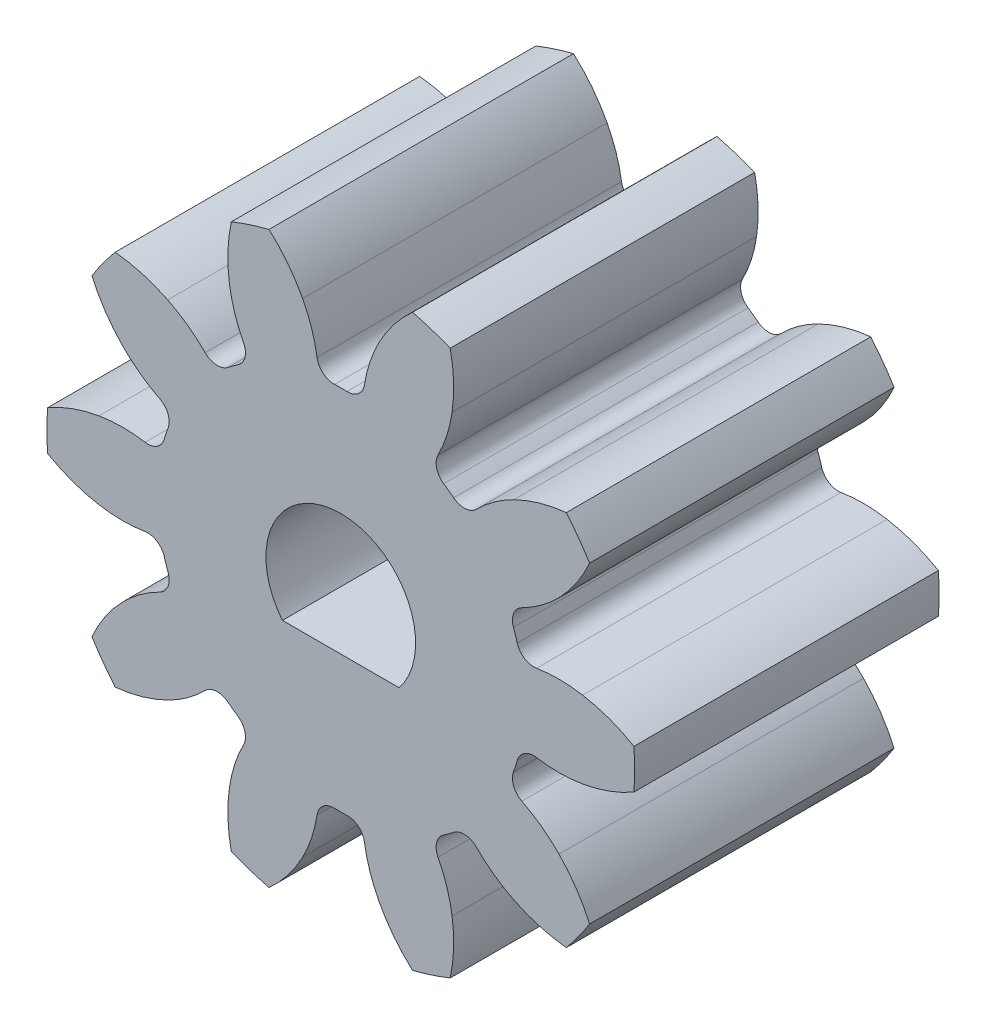
SolidWorks part; units mm, degrees
material "Plain Carbon Steel"
ref_plane "Front" through (0, 0, 0) normal (0, 0, 1) x (1, 0, 0)
ref_plane "Top" through (0, 0, 0) normal (0, 1, 0) x (1, 0, 0)
ref_plane "Right" through (0, 0, 0) normal (1, 0, 0) x (0, 0, -1)
sketch "Sketch1" plane through (0, 0, 0) normal (0, 0, 1) x (1, 0, 0)
  line L0 (0, 0) -> (4.9063, 0) construction
  line L1 (4.9063, 0) -> (5.8875, 0) construction
  circle A0 centre (0, 0) radius 4.9063 construction
  circle A1 centre (0, 0) radius 5.8875
  dimension "pitch_diameter" = 9.8125
  dimension "addendum" = 0.9813
extrude "BLANK DISK" add sketch "Sketch1" along normal mid plane 6.1
sketch "Sketch2" plane through (0, 0, 3.05) normal (0, 0, 1) x (1, 0, 0)
  line L0 (0, 0) -> (3.6797, 0) construction
  line L1 (3.6797, 0) -> (4.9063, 0) construction
  line L2 (0, 0) -> (-5.8875, 0) construction
  line L3 (0, 0) -> (-4.7631, -3.4606) construction
  line L4 (-4.9857, -3.1314) -> (-4.373, -2.2244) construction
  line L5 (-4.373, -2.2244) -> (-3.3636, -1.4921) construction
  line L6 (-5.8741, -0.3971) -> (-4.8453, -0.7708) construction
  line L7 (-4.8453, -0.7708) -> (-3.5982, -0.7699) construction
  line L8 (-3.92, -2.848) -> (-4.373, -2.2244) construction
  line L9 (-4.8453, -0.7708) -> (-4.8453, 0) construction
  line L12 (0, 0) -> (-4.8453, -0.7708) construction
  line L13 (0, 0) -> (-4.373, -2.2244) construction
  line L14 (-4.373, -2.2244) -> (-2.8975, -5.1252) construction
  line L15 (-4.8453, -0.7708) -> (-5.3566, 2.4433) construction
  line L16 (-4.373, -2.2244) -> (-4.8453, -0.7708) construction
  line L17 (-3.4996, -1.1371) -> (-3.5982, -0.7699) construction
  line L18 (-3.4996, -1.1371) -> (-3.3636, -1.4921) construction
  circle A0 centre (0, 0) radius 4.9063 construction
  circle A1 centre (0, 0) radius 3.6797 construction
  circle A2 centre (0, 0) radius 5.8875 construction
  arc A3 (-4.9857, -3.1314) -> (-5.8741, -0.3971) centre (0, 0) cw
  arc A4 (-3.3636, -1.4921) -> (-3.5982, -0.7699) centre (0, 0) cw construction
  arc A6 (-4.9857, -3.1314) -> (-4.373, -2.2244) centre (-2.1651, -4.3763) cw
  arc A7 (-5.8741, -0.3971) -> (-4.8453, -0.7708) centre (-4.3239, 2.2679) ccw
  arc A8 (-4.373, -2.2244) -> (-3.6276, -1.6782) centre (-2.3682, -4.1783) cw
  arc A9 (-4.8453, -0.7708) -> (-3.9212, -0.7746) centre (-4.3719, 1.9883) ccw
  arc A10 (-3.6276, -1.6782) -> (-3.4593, -1.2544) centre (-3.7821, -1.3715) ccw
  arc A11 (-3.9212, -0.7746) -> (-3.5359, -1.0185) centre (-3.8659, -1.1135) cw
  arc A12 (-3.4593, -1.2544) -> (-3.5359, -1.0185) centre (0, 0) cw
  dimension "D12" = 3.0831
  dimension "D3" = 36
  dimension "D4" = 0.7708
  dimension "D5" = 0.7708
  dimension "D11" = 1.5285
  dimension "D14" = 9
  dimension "D15" = 9
  dimension "base_fillet" = 0.3434
  dimension "pitch_diameter" = 9.8125
  dimension "deddendum" = 1.2266
extrude "GEAR TOOTH CUT" cut sketch "Sketch2" against normal through all
ref_axis "CENTER AXIS" through (0, 0, 50) along (0, 0, -1)
pattern_circular "GEAR TEETH REVOLVE" count 10 over 360 about axis through (0, 0, 50) along (0, 0, -1) of "GEAR TOOTH CUT"
sketch "Sketch3" plane through (0, 0, 3.05) normal (0, 0, 1) x (1, 0, 0)
  line L0 (-1.1691, -0.9398) -> (1.1691, -0.9398)
  arc A0 (1.1691, -0.9398) -> (-1.1691, -0.9398) centre (0, 0) ccw
  dimension "D1" = 3
  dimension "D2" = 0.9398
extrude "HUB EXTRUDE" cut sketch "Sketch3" against normal through all
equation "\"N_teeth\"= 10.000000"
equation "\"pitch_diameter\"= 9.8125mm"
equation "\"Pd\"= \"N_teeth\" / \"pitch_diameter\""
equation "\"addendum\"=1.000/\"Pd\""
equation "\"face_width\"= 6.1mm"
equation "\"deddendum\"=1.250/\"Pd\""
equation "\"D3@Sketch2\" = 360/\"N_teeth\""
equation "\"tooth_thickness\"=1.571/\"Pd\""
equation "\"D4@Sketch2\" = \"tooth_thickness\"/2"
equation "\"D5@Sketch2\" = \"tooth_thickness\"/2"
equation "\"Pressure_Angle\"= 20.000000"
equation "\"base_fillet\"=0.35/\"Pd\""
equation "\"D12@Sketch2\" = 2*\"tooth_thickness\""
equation "\"hub_diameter\"= .3"
equation "\"bore\"= .375"
equation "\"hub_projection\"= 0.00000"
equation "\"sss_diam\"=0.062500"
equation "\"stepperaxleflat\"=.037in"
equation "\"D2@Sketch3\"=\"stepperaxleflat\""
equation "\"stepperaxlerad\"=0.11811024in"
equation "\"D1@Sketch3\"=\"stepperaxlerad\""
equation "\"CageLeftBottomEdge\"=22.11mm"
equation "\"CageLeftTopEdge\"=22.11mm"
equation "\"CageRightBottomEdge\"=21.63mm"
equation "\"CageRightTopEdge\"=21.63mm"
equation "\"CageHeight\"=86.04mm"
equation "\"CageLength\"=73.76mm"
equation "\"CageTopScrewClearance\"=10mm"
equation "\"CageBottomScrewClearance\"=25mm"
equation "\"CageLeftTopDepth\"= 11.65mm"
equation "\"CageLeftBottomDepth\"=11.11mm"
equation "\"CageLeftTopHeight\"=8.56175mm"
equation "\"CageLeftBottomHeight\"=16mm"
equation "\"CageRightTopDepth\"= 11.05mm"
equation "\"CageRightBottomDepth\"=10.58mm"
equation "\"CageRightTopHeight\"=9.6mm"
equation "\"CageRightBottomHeight\"=15.49mm"
equation "\"CageLeftTopChannelDepth\"=2.41908mm"
equation "\"CageLeftBottomChannelDepth\"=2.588mm"
equation "\"CageLeftChannelHeight\"=11.7mm"
equation "\"CageRightTopChannelDepth\"=2.32mm"
equation "\"CageRightBottomChannelDepth\"=2.318mm"
equation "\"CageRightChannelHeight\"=10mm"
equation "\"CageChanRelHeight\"=23.99mm"
equation "\"CageChanRelDepth\"=5.492mm"
equation "\"CageChamberRadius\"=16.261mm"
equation "\"CageScrewDiameter\"=4.8mm"
equation "\"CageSetScrewDiameter\"=3.5mm"
equation "\"CageAxleRadius\"=6.639mm"
equation "\"CageAxleKeyHeight\"=1.619mm"
equation "\"CageAxleKeyWidth\"=2.662mm"
equation "\"CageHoseWindowWidth\"=16.29mm"
equation "\"CageHoseWindowHeight\"=26.5mm"
equation "\"CageHoseWindow-Edge\"=8.89mm"
equation "\"CageScrew-VerticalEdge\"=5.0mm"
equation "\"CageScrew-HorizontalEdge\"=7.5mm"
equation "\"CageScrew-HoseCornerScrewEdge\"=4.45mm"
equation "\"CageAxle-BottomEdge\"=56.05mm"
equation "\"CageAxle-FrontEdge\"=46.03mm"
equation "\"CageBackSetScrew-Axle\"=40mm"
equation "\"CageFrontSetScrew-Axle\"=22mm"
equation "\"CageVelocityWindow-BackEdge\"=34.8mm"
equation "\"CageVelocityWindow-BottomEdge\"=27.55mm"
equation "\"CageVelocityWindowHeight\"=22.29mm"
equation "\"CageVelocityWindowWidth\"=12.61mm"
equation "\"TriggerSlot-BottomEdge\"=6.35mm"
equation "\"TriggerSlot-FrontEdge\"=15mm"
equation "\"TriggerSlotSize\"=6.7mm"
equation "\"TriggerRackOffset\"=.236224in"
equation "\"TriggerSlotSizeInt\"=.25in"
equation "\"MotorMountLegLength\"=.25in"
equation "\"GearOffset\"=.264907in"
equation "\"TriggerSlotSpacing\"=.25in"
equation "\"TriggerMiniSlotWidth\"=3.5mm"
equation "\"TriggerRackWidth\"=6.5mm"
equation "\"whitemotordepth\"=11.27mm"
equation "\"whitemotorbackdepth\"=3.845mm"
equation "\"whitemotoraxledepth\" = 3.5mm"
equation "\"whitemotoraxleoffset\"=11.4mm"
equation "\"whitemotorwidth\"=12.07mm"
equation "\"whitemotorheight\"=16.68mm"
equation "\"whitemotorcylinderlength\" =13.04mm"
equation "\"whitemotorcylinderradius\"=3.845mm"
equation "\"whitemotorcylinderoffset\"=2.35mm"
equation "\"whitemotorcutoutlength\"=1.88mm"
equation "\"whitemotorouterrad\"=5mm"
equation "\"whitemotorinnerrad\"=2.95mm"
equation "\"elasticracklength\"=2in"
equation "\"elasticrackpegsize\"=.25in"
equation "\"elasticrackpegbuffer\"=.125in"
equation "\"elasticrackpegspacing\"=1.76476378in"
equation "\"elasticbaybuffer\"=.25in"
equation "\"elasticdepth\"=.125in"
equation "\"elasticbaydepth\"=.75in"
equation "\"motormountwidth\"=12mm"
equation "\"motormountcornerfillet\"=3mm"
equation "\"pandiscradius\"=14in"
equation "\"towermaterialwidth\"=.25in"
equation "\"towerslotlength\"=.5in"
equation "\"towermarkerspace\"=5in"
equation "\"towerslothorizoffset\"=1in"
equation "\"towerslothorizspacing\"=2in"
equation "\"towerslotvertoffset\"=3in"
equation "\"towerslotvertspacing\"=1in"
equation "\"towerheight\"=12in"
equation "\"towerupslot\"=1in"
equation "\"toweraxle\"=.5in"
equation "\"stepperouterrad\"=10mm"
equation "\"stepperscrewsize\"=3.45mm"
equation "\"stepperscrewc2c\"=49.5mm"
equation "\"stepperdepthoffset\"=24mm"
equation "\"stepperhorizoffset\"=22.91mm"
equation "\"shaftslotOD\"=18.8mm"
equation "\"shaftslotID\"=13.28mm"
equation "\"shaftkeywidth\"=2.67mm"
equation "\"shaftkeydepth\"=1.8mm"
equation "\"shaftcollartotaldepth\"=12.5mm"
equation "\"shaftsquaredepth\"=6mm"
equation "\"shaftsetscrewsize\"=3.5mm"
equation "\"shaftkeytightdepth\"=1.85mm"
equation "\"shaftslottightID\"=12.78mm"
equation "\"shaftsetscrewoffset\"=9mm"
equation "\"cagecollartotaldepth\"=10mm"
equation "\"cagecollartotalwidth\"=35mm"
equation "\"cagecollarbasedepth\"=4mm"
equation "\"ajaxaxlesize\"=3.87mm"
equation "\"ajaxinnercut\"=2.3mm"
equation "\"ajaxwidth\"=6.1mm"
equation "\"ajaxdiametral\"=25.8854"
equation "\"ajax4020gap\"=29.5mm"
equation "\"ajax4010gap\"=24.5mm"
equation "\"ajaxcutoutdepth\"=2.3mm"
equation "\"ajax20hubbuffer\"=6.1mm"
equation "\"ajax20hubholeoffset\"=.19685in"
equation "\"ajax20hubholesize\"=.059055in"
equation "\"ajax20cutoutint\"=13.4mm"
equation "\"ajax40hubholesize\"=7.21mm"
equation "\"ajax40hubholeoffset\"=10mm"
equation "\"ajax40hubbuffer\"=8.9mm"
equation "\"ajax40cutoutint\"=32.6mm"
equation "\"bearingpandiscrad\"=6.8in"
equation "\"bearingpandiscang\"=48.75deg"
equation "\"bearingclearholedist\"=4.7345in"
equation "\"bearingclearholesize\"=.5in"
equation "\"bearingclearholeang\"=22.5deg"
equation "\"bearingmountholedist\"=4.25in"
equation "\"bearingwirehole\"=1.5in"
equation "\"no6diam\"=.146in"
equation "\"gearhubintdiam\"=30mm"
equation "\"gearhubintwid\"=15mm"
equation "\"towerspeedwidth\"=2in"
equation "\"towerspeedheight\"=8in"
equation "\"towerspeedgap\"=2in"
equation "\"shortconangle\"=20deg"
equation "\"shortconlen\"=.875in"
equation "\"longconlen\"=1.25in"
equation "\"longconangle\"=15deg"
